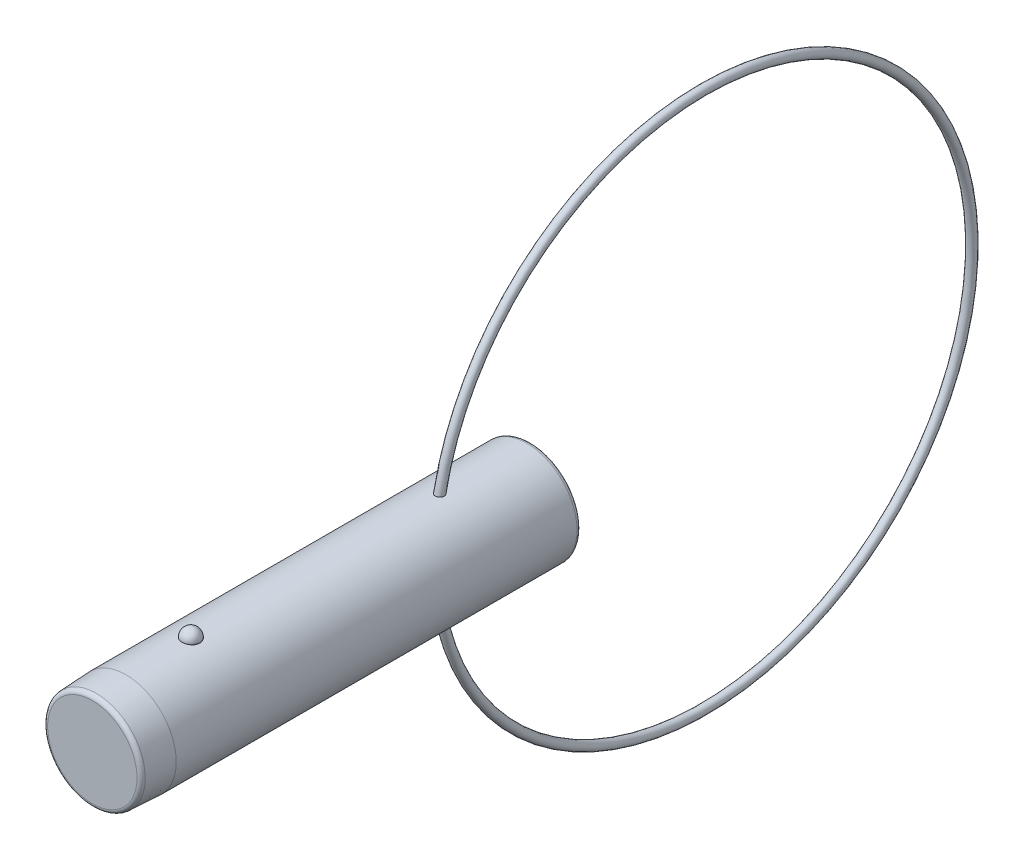
SolidWorks part; units mm, degrees
material "Alliage de zinc AC41A, brut"
ref_plane "Plan de face" through (0, 0, 0) normal (0, 0, 1) x (1, 0, 0)
ref_plane "Plan de dessus" through (0, 0, 0) normal (0, 1, 0) x (1, 0, 0)
ref_plane "Plan de droite" through (0, 0, 0) normal (1, 0, 0) x (0, 0, -1)
sketch "Esquisse1" plane through (0, 0, 0) normal (0, 0, 1) x (1, 0, 0)
  circle A0 centre (0, 0) radius 2.3813
  dimension "D1" = 4.7625
extrude "Boss.-Extru.1" add sketch "Esquisse1" against normal blind 20.7518
sketch "Esquisse4" plane through (0, 0, 0) normal (1, 0, 0) x (0, 0, -1)
  line L0 (0, 2.3813) -> (20.7518, 2.3813) construction
sketch "Esquisse5" plane through (0, 0, 0) normal (1, 0, 0) x (0, 0, -1)
  line L0 (1.5875, 2.3813) -> (0, 2.3051)
  line L1 (0, 2.3051) -> (0, 2.3813)
  line L2 (0, 2.3813) -> (1.5875, 2.3813)
  line L3 (0, 0) -> (20.7518, 0) construction
  line L4 (20.7518, -2.3813) -> (20.7518, 2.3813) construction
  dimension "D1" = 0.0762
  dimension "D2" = 1.5875
revolve "Enlèvement de matière-Révolution1" cut sketch "Esquisse5" angle 360 about L3
sketch "Esquisse6" plane through (0, 0, 0) normal (1, 0, 0) x (0, 0, -1)
  line L2 (4.6609, 2.3813) -> (4.6609, 2.8003)
  line L3 (0, 2.3813) -> (20.7518, 2.3813) construction
  line L4 (5.08, 2.3813) -> (4.6609, 2.3813)
  line L5 (4.6609, 2.3813) -> (4.6609, 3.2529) construction
  arc A0 (4.6609, 2.8003) -> (5.08, 2.3813) centre (4.6609, 2.3812) cw
  dimension "D1" = 0.4191
  dimension "D2" = 5.08
  dimension "D3" = 0.4191
revolve "Révolution1" add sketch "Esquisse6" angle 360 about L5
sketch "Esquisse8" plane through (0, 2.3813, 0) normal (0, -1, 0) x (1, 0, 0)
  line L0 (0, 0) -> (0, -20.7518) construction
  circle A0 centre (0, -4.6609) radius 0.4191
  circle A1 centre (0, -4.6609) radius 0.4191 construction
extrude "Boss.-Extru.2" add sketch "Esquisse8" along normal up to next
fillet "Congé1" radius 0.2 2 edges at (2.3813, 0, -20.7518) (2.3051, 0, 0)
ref_plane "Plan1" through (0, 0, -16.002) normal (0, 0, -1) x (-1, 0, 0)
ref_plane "Plan2" through (0, 0, -28.9116) normal (0, 0, -1) x (-1, 0, 0)
sketch "Esquisse9" plane through (0, 0, -28.9116) normal (0, 0, -1) x (-1, 0, 0)
  line L0 (0, 12.7) -> (0, 0) construction
  line L1 (0, 0) -> (-5.9972, 0) construction
  circle A0 centre (0, 12.7) radius 0.2095
  circle A1 centre (0, 0) radius 2.1812 construction
  dimension "D1" = 0.4191
  dimension "D2" = 12.7
revolve "Révolution2" add sketch "Esquisse9" angle 360 about L1
